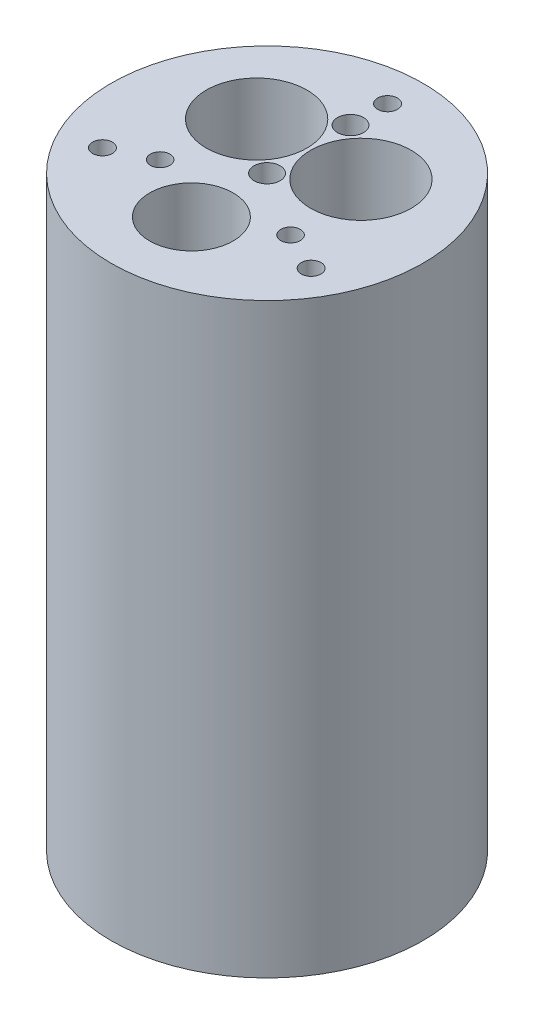
SolidWorks part; units mm, degrees
material "PLA"
ref_plane "Front Plane" through (0, 0, 0) normal (0, 0, 1) x (1, 0, 0)
ref_plane "Top Plane" through (0, 0, 0) normal (0, 1, 0) x (1, 0, 0)
ref_plane "Right Plane" through (0, 0, 0) normal (1, 0, 0) x (0, 0, -1)
sketch "Sketch1" plane through (0, 0, 0) normal (0, 1, 0) x (1, 0, 0)
  circle A0 centre (0, 0) radius 37.973
  dimension "D1" = 75.946
extrude "Boss-Extrude1" add sketch "Sketch1" along normal blind 142.8496
sketch "Sketch2" plane through (0, 142.8496, 0) normal (0, 1, 0) x (1, 0, 0)
  circle A0 centre (0, 29.337) radius 2.413
  circle A1 centre (25.4066, -14.6685) radius 2.413
  circle A2 centre (-25.4066, -14.6685) radius 2.413
  point P9 (0, 0)
  dimension "D2" = 4.826
  dimension "D1" = 29.337
extrude "Cut-Extrude1" cut sketch "Sketch2" against normal through all
sketch "Sketch3" plane through (0, 142.8496, 0) normal (0, 1, 0) x (1, 0, 0)
  line L0 (-12.7, 10.16) -> (12.7, 10.16) construction
  circle A0 centre (25.4066, -14.6685) radius 2.413 construction
  circle A1 centre (-12.7, 10.16) radius 12.2555
  circle A3 centre (0, 29.337) radius 2.413 construction
  circle A4 centre (-25.4066, -14.6685) radius 2.413 construction
  circle A5 centre (25.4066, -14.6685) radius 2.413 construction
  circle A6 centre (0, 29.337) radius 2.413 construction
  circle A7 centre (-25.4066, -14.6685) radius 2.413 construction
  circle A8 centre (12.7, 10.16) radius 12.2555
  point P13 (0, 10.16)
  dimension "D1" = 24.511
  dimension "D2" = 24.511
  dimension "D3" = 25.4
  dimension "D4" = 10.16
extrude "Cut-Extrude2" cut sketch "Sketch3" against normal through all
ref_axis "Axis1" through (0, -7.1425, 0) along (0, 1, 0)
ref_plane "Plane1" through (0, 71.4248, 0) normal (0, -1, 0) x (-1, 0, 0)
sketch "Sketch4" plane through (0, 142.8496, 0) normal (0, 1, 0) x (1, 0, 0)
  line L0 (-12.7, 10.16) -> (12.7, 10.16) construction
  circle A0 centre (0, 20.32) radius 3.175
  circle A1 centre (0, 0) radius 3.175
  circle A2 centre (12.7, 10.16) radius 12.2555 construction
  circle A3 centre (-12.7, 10.16) radius 12.2555 construction
  circle A4 centre (12.7, 10.16) radius 12.2555 construction
  circle A5 centre (-12.7, 10.16) radius 12.2555 construction
  dimension "D1" = 6.35
  dimension "D2" = 6.35
  dimension "D3" = 10.16
  dimension "D4" = 10.16
extrude "Cut-Extrude3" cut sketch "Sketch4" against normal blind 6.35
sketch "Sketch5" plane through (0, 142.8496, 0) normal (0, 1, 0) x (1, 0, 0)
  circle A0 centre (0, -18.415) radius 4.1275 construction
  circle A1 centre (0, -18.415) radius 10.16
  dimension "D1" = 20.32
  dimension "D2" = 8.255
  dimension "D3" = 18.415
extrude "Cut-Extrude4" cut sketch "Sketch5" against normal blind 17.78
sketch "Sketch6" plane through (0, 142.8496, 0) normal (0, 1, 0) x (1, 0, 0)
  line L0 (-15.875, -10.16) -> (15.875, -10.16) construction
  line L1 (0, 0) -> (0, -10.16) construction
  circle A0 centre (15.875, -10.16) radius 2.3813
  circle A1 centre (-15.875, -10.16) radius 2.3813
  dimension "D1" = 4.7625
  dimension "D2" = 4.7625
  dimension "D3" = 10.16
  dimension "D4" = 31.75
extrude "Cut-Extrude5" cut sketch "Sketch6" against normal through all both and the other way through all
equation "\"D1@Sketch1\"=3.01-\"tolerance_body_tube\""
equation "\"tolerance_body_tube\"= 0.02"
equation "\"tolerance_threaded_rods\"= 0.02"
equation "\"tolerance_peregrines\"= 0.03"
equation "\"D1@Sketch3\"=\"D2@Sketch3\""
equation "\"D2@Sketch3\"=0.935+\"tolerance_peregrines\""
equation "\"D2@Sketch2\"=0.170+\"tolerance_threaded_rods\""
